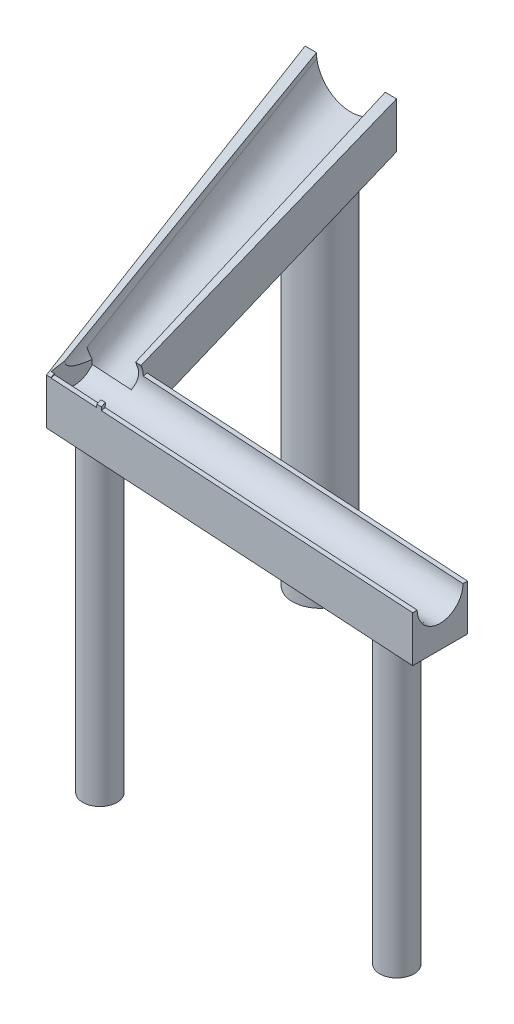
SolidWorks part; units mm, degrees
ref_plane "前基準面" through (0, 0, 0) normal (0, 0, 1) x (1, 0, 0)
ref_plane "上基準面" through (0, 0, 0) normal (0, 1, 0) x (1, 0, 0)
ref_plane "右基準面" through (0, 0, 0) normal (1, 0, 0) x (0, 0, -1)
sketch "草圖3" plane through (0, 0, 0) normal (0, 0, 1) x (1, 0, 0)
  line L0 (-64.6619, 0) -> (74.149, 0) construction
  line L2 (0, 77.769) -> (0, -86.0078) construction
  line L3 (0, 0) -> (106, 0)
  line L4 (0, 0) -> (0, 91.75)
  line L5 (0, 91.75) -> (106, 91.75)
  line L6 (106, 0) -> (106, 91.75)
  dimension "D1" = 91.75
  dimension "D2" = 106
sketch "草圖6" plane through (0, 0, 0) normal (1, 0, 0) x (0, 0, -1)
  line L1 (0, 0) -> (77.5, 0)
  line L2 (0, 0) -> (0, 91.75)
  line L3 (0, 91.75) -> (77.5, 91.75)
  line L4 (77.5, 0) -> (77.5, 91.75)
  dimension "D1" = 91.75
  dimension "D2" = 77.5
sketch "草圖7" plane through (0, 0, 0) normal (0, 0, 1) x (1, 0, 0)
  line L0 (26, 78.75) -> (106, 73.7694)
  line L1 (106, 0) -> (106, 91.75) construction
  line L2 (26, 68.7306) -> (106, 63.75)
  line L3 (26, 78.75) -> (26, 68.7306)
  line L4 (106, 73.7694) -> (106, 63.75)
  point P6 (26, 81.5827)
  dimension "D1" = 10
  dimension "D2" = 80
  dimension "D3" = 63.75
  dimension "D4" = 15
extrude "填料-伸長3" add sketch "草圖7" against normal blind 12
ref_plane "平面2" through (0, 0, -77.5) normal (0, 0, 1) x (1, 0, 0)
sketch "草圖12" plane through (0, 0, -77.5) normal (0, 0, 1) x (1, 0, 0)
  line L0 (0, 91.75) -> (106, 91.75) construction
  line L1 (5, 91.75) -> (7.5, 91.75)
  line L2 (5, 91.75) -> (5, 81.75)
  line L3 (5, 81.75) -> (25, 81.75)
  line L4 (25, 91.75) -> (25, 81.75)
  line L5 (0, 0) -> (0, 91.75) construction
  line L6 (22.5, 91.75) -> (25, 91.75)
  line L7 (15, 97.2461) -> (15, 77.4422) construction
  arc A0 (7.5, 91.75) -> (22.5, 91.75) centre (15, 91.75) ccw
  point P13 (0, 0)
  point P14 (0, 0)
  dimension "D4" = 15
  dimension "D1" = 5
  dimension "D2" = 20
  dimension "D3" = 10
  dimension "D5" = 2.5
  dimension "D6" = 10
sketch "草圖13" plane through (0, 0, 0) normal (0, 0, 1) x (1, 0, 0)
  line L0 (26, 78.75) -> (26, 68.7306) construction
  line L1 (26, 78.75) -> (26, 68.7306)
  line L2 (26, 78.75) -> (27, 78.75)
  line L3 (38, 78.75) -> (38, 67.9835)
  line L4 (26, 68.7306) -> (106, 63.75) construction
  line L5 (38, 67.9835) -> (26, 68.7306)
  line L6 (37, 78.75) -> (38, 78.75)
  arc A0 (27, 78.75) -> (37, 78.75) centre (32, 78.75) ccw
  dimension "D2" = 10
  dimension "D1" = 12
  dimension "D3" = 6
  dimension "D4" = 1
loft "疊層拉伸2" add profiles "草圖13", "草圖12"
sketch "草圖15" plane through (106, 0, 0) normal (1, 0, 0) x (0, 0, -1)
  line L1 (0, 73.7694) -> (12, 73.7694) construction
  circle A0 centre (6, 73.7694) radius 5
  dimension "D1" = 10
sketch "草圖16" plane through (26, 0, 0) normal (-1, 0, 0) x (0, 0, 1)
  line L0 (0, 0) -> (0, 91.75) construction
  line L1 (0, 0) -> (0, 91.75) construction
  line L2 (0, 78.75) -> (-12, 78.75) construction
  circle A0 centre (-6, 78.75) radius 5
  dimension "D2" = 10
  dimension "D1" = 12
loft "除料-疊層拉伸2" cut profiles "草圖16", "草圖15" connector at (26, 78.75, -1) connector at (106, 73.3938, -1.0141)
sketch "草圖21" plane through (0, 0, -77.5) normal (0, 0, -1) x (-1, 0, 0)
  line L0 (0, 91.75) -> (-106, 91.75) construction
  circle A0 centre (-15, 91.75) radius 7.5
  dimension "D1" = 15
ref_plane "平面3" through (0, 0, -10) normal (0, 0, 1) x (1, 0, 0)
sketch "草圖24" plane through (0, 0, -10) normal (0, 0, 1) x (1, 0, 0)
  circle A0 centre (30.0793, 78.0136) radius 5.25
  dimension "D1" = 10.5
loft "除料-疊層拉伸4" cut profiles "草圖24", "草圖21" connector at (35.3293, 78.0136, -10) connector at (22.4996, 91.8306, -77.5)
sketch "草圖25" plane through (0, 0, 0) normal (0, 1, 0) x (1, 0, 0)
  circle A0 centre (96.9675, 5.5906) radius 3.75
  circle A1 centre (32.0913, 5.5906) radius 3.75
  circle A2 centre (17.0364, 68.7296) radius 6
  point P4 (17.0364, 68.7296)
  dimension "D1" = 7.5
  dimension "D2" = 12
extrude "填料-伸長5" add sketch "草圖25" along normal up to next
